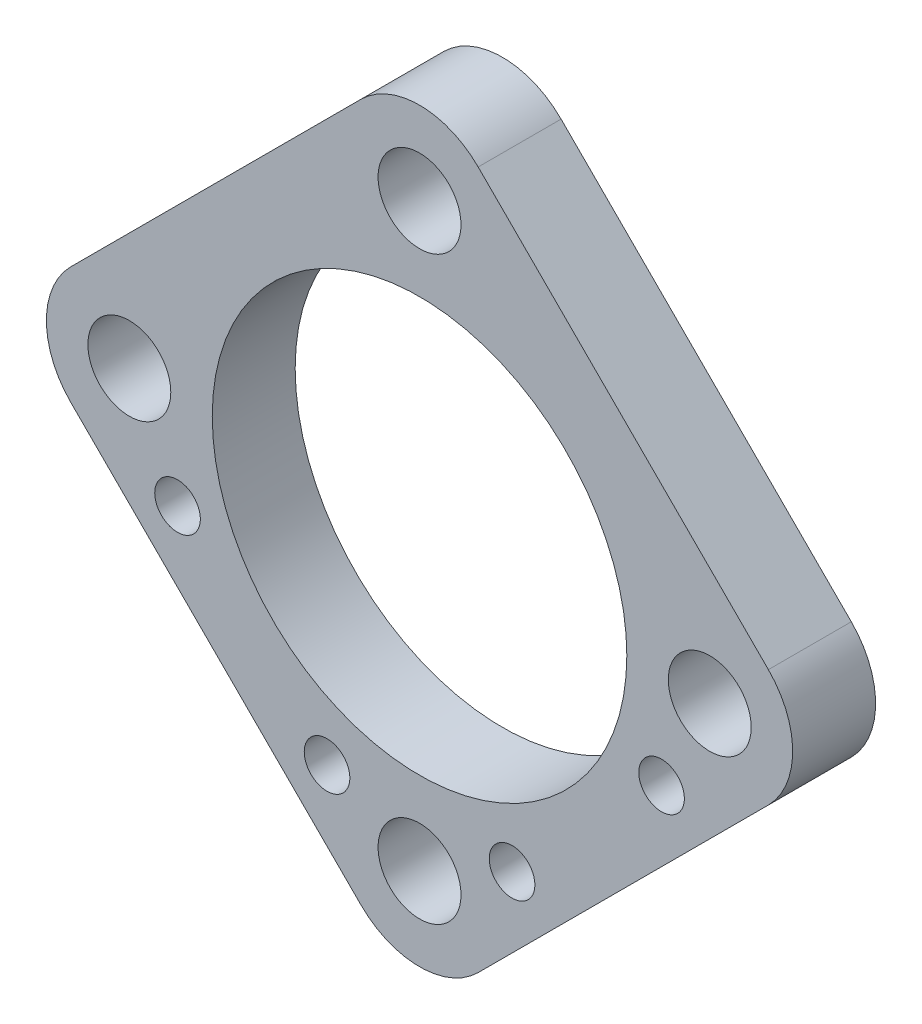
SolidWorks part; units mm, degrees
ref_plane "Płaszczyzna przednia" through (0, 0, 0) normal (0, 0, 1) x (1, 0, 0)
ref_plane "Płaszczyzna górna" through (0, 0, 0) normal (0, 1, 0) x (1, 0, 0)
ref_plane "Płaszczyzna prawa" through (0, 0, 0) normal (1, 0, 0) x (0, 0, -1)
sketch "Szkic1" plane through (0, 0, 0) normal (0, 0, 1) x (1, 0, 0)
  line L0 (-42.0711, 7.0711) -> (-7.0711, 42.0711)
  line L1 (7.0711, 42.0711) -> (42.0711, 7.0711)
  line L2 (-7.0711, -42.0711) -> (-42.0711, -7.0711)
  line L3 (42.0711, -7.0711) -> (7.0711, -42.0711)
  circle A1 centre (-35, 0) radius 5
  circle A2 centre (0, 35) radius 5
  circle A3 centre (35, 0) radius 5
  circle A4 centre (0, -35) radius 5
  circle A5 centre (0, 0) radius 25
  arc A7 (-42.0711, 7.0711) -> (-42.0711, -7.0711) centre (-35, 0) ccw
  arc A9 (42.0711, -7.0711) -> (42.0711, 7.0711) centre (35, 0) ccw
  arc A10 (-7.0711, -42.0711) -> (7.0711, -42.0711) centre (0, -35) ccw
  arc A12 (7.0711, 42.0711) -> (-7.0711, 42.0711) centre (0, 35) ccw
  dimension "D1" = 35
  dimension "D2" = 10
  dimension "D3" = 10
  dimension "D4" = 10
  dimension "D5" = 10
  dimension "D6" = 50
  dimension "D7" = 10
  dimension "D10" = 10
  dimension "D8" = 70
  dimension "D9" = 70
extrude "Dodanie-wyciągnięcie1" add sketch "Szkic1" along normal blind 10 contours A4 A3 A2 A1 A5 | A4 A1 A2 A3 region at (-23.6711, 23.6711, 0)
sketch "Szkic2" plane through (0, 0, 0) normal (0, 0, -1) x (-1, 0, 0)
  line L0 (29.1881, -11.4688) -> (11.1569, -29.5)
  line L1 (-11.1569, -29.5) -> (-29.1881, -11.4688)
  line L2 (-42.0711, -7.0711) -> (-7.0711, -42.0711) construction
  line L3 (7.0711, -42.0711) -> (42.0711, -7.0711) construction
  line L4 (11.1569, -29.5) -> (-11.1569, -29.5)
  line L5 (29.1881, -11.4688) -> (-29.1881, -11.4688)
  circle A0 centre (11.1569, -29.5) radius 2.75
  circle A1 centre (29.1881, -11.4688) radius 2.75
  circle A2 centre (-11.1569, -29.5) radius 2.75
  circle A3 centre (-29.1881, -11.4688) radius 2.75
  circle A4 centre (35, 0) radius 5 construction
  circle A5 centre (0, -35) radius 5 construction
  dimension "D1" = 5.5
  dimension "D3" = 4
  dimension "D5" = 4
  dimension "D4" = 5.5
  dimension "D2" = 25.5
extrude "Wytnij-wyciągnięcie1" cut sketch "Szkic2" against normal through all both and the other way through all contours A1 | A0 | A2 | A3
